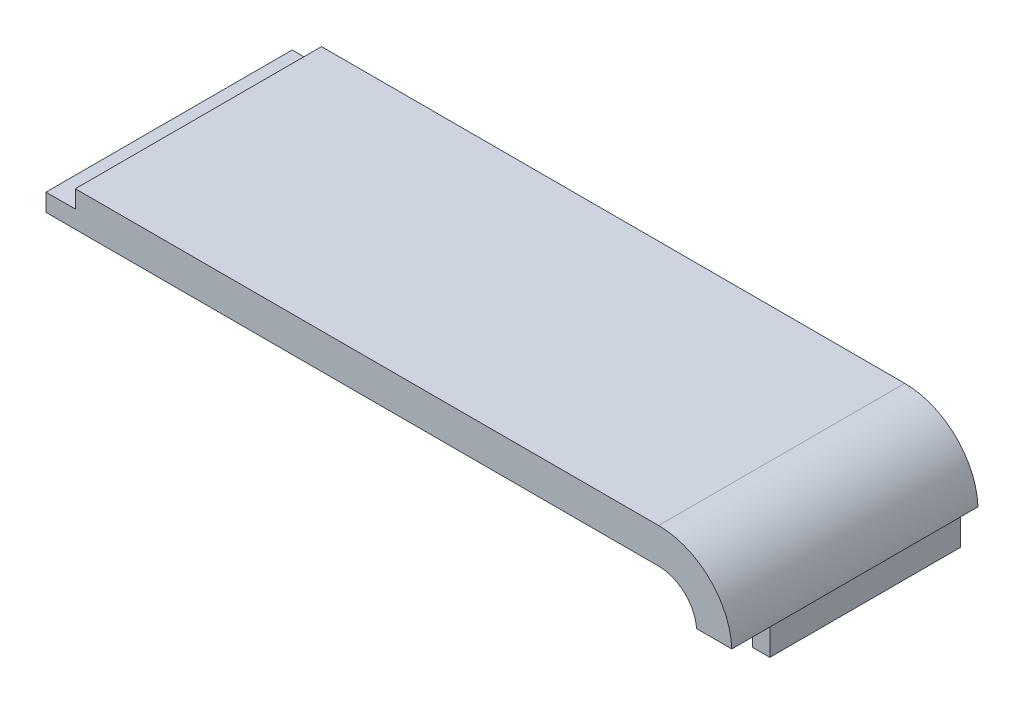
SolidWorks part; units mm, degrees
ref_plane "Front Plane" through (0, 0, 0) normal (0, 0, 1) x (1, 0, 0)
ref_plane "Top Plane" through (0, 0, 0) normal (0, 1, 0) x (1, 0, 0)
ref_plane "Right Plane" through (0, 0, 0) normal (1, 0, 0) x (0, 0, -1)
sketch "Sketch1" plane through (0, 0, 0) normal (0, 0, 1) x (1, 0, 0)
  line L1 (-18.2903, 6.0242) -> (26.5097, 6.0242)
  line L2 (-18.2903, 6.0242) -> (-18.2903, 1.2242)
  line L3 (-18.2903, 1.2242) -> (26.5097, 1.2242)
  line L4 (26.5097, 6.0242) -> (26.5097, 1.2242)
  dimension "D1" = 44.8
  dimension "D2" = 4.8
extrude "Boss-Extrude1" add sketch "Sketch1" along normal blind 16.8
fillet "Fillet1" radius 5 1 edges at (26.5097, 6.0242, 8.4)
sketch "Sketch2" plane through (0, 0, 0) normal (0, 0, -1) x (-1, 0, 0)
  line L1 (-24.106, 1.2242) -> (18.2903, 1.2242)
  line L2 (-21.5137, 3.6242) -> (18.2903, 3.6242)
  line L3 (-21.5137, 3.6242) -> (18.2903, 3.6242)
  line L4 (18.2903, 1.2242) -> (-26.5097, 1.2242) construction
  line L5 (18.2903, 1.2242) -> (18.2903, 3.6242)
  arc A2 (-21.5137, 3.6242) -> (-24.1116, 1.1282) centre (-21.5137, 1.0242) ccw
  arc A3 (-21.5137, 3.6242) -> (-24.106, 1.2242) centre (-21.5137, 1.0242) ccw
  dimension "D1" = 2.4
extrude "Cut-Extrude1" cut sketch "Sketch2" against normal through all
sketch "Sketch3" plane through (0, 1.2242, 0) normal (0, -1, 0) x (1, 0, 0)
  line L0 (24.106, 0) -> (26.5097, 0) construction
  line L2 (24.106, 13) -> (24.106, 0)
  line L3 (24.106, 0) -> (25.306, 0)
  line L4 (25.306, 13) -> (25.306, 0)
  line L5 (24.106, 13) -> (25.306, 13)
  dimension "D1" = 1.2
  dimension "D2" = 13
extrude "Boss-Extrude2" add sketch "Sketch3" along normal blind 3 contours L4 L3 L2 L5
sketch "Sketch4" plane through (-18.2903, 0, 0) normal (-1, 0, 0) x (0, 0, 1)
  line L0 (16.8, 6.0242) -> (16.8, 3.6242) construction
  line L1 (0, 3.6242) -> (16.8, 3.6242)
  line L2 (0, 3.6242) -> (0, 4.8242)
  line L3 (0, 4.8242) -> (16.8, 4.8242)
  line L4 (16.8, 3.6242) -> (16.8, 4.8242)
  dimension "D1" = 1.2
extrude "Boss-Extrude3" add sketch "Sketch4" along normal blind 2
sketch "Sketch5" plane through (0, 0, 0) normal (0, 0, -1) x (-1, 0, 0)
  line L1 (-24.106, -1.7758) -> (-24.106, 1.2242) construction
  line L2 (-18.106, -0.7758) -> (-18.106, 3.6242)
  line L3 (20.2903, 3.6242) -> (-21.5137, 3.6242) construction
  line L4 (-18.106, 3.6242) -> (-21.5137, 3.6242)
  line L5 (-24.106, -0.7758) -> (-24.106, 1.2242)
  line L8 (-24.106, -0.7758) -> (-18.106, -0.7758)
  line L9 (-21.5137, 6.0242) -> (18.2903, 6.0242) construction
  arc A0 (-21.5137, 3.6242) -> (-24.106, 1.2242) centre (-21.5137, 1.0242) ccw
  circle A2 centre (-21.5137, 1.0242) radius 1
  dimension "D3" = 2
  dimension "D1" = 6.8
  dimension "D2" = 6
extrude "Boss-Extrude4" add sketch "Sketch5" against normal blind 2
fillet "Fillet2" radius 2 1 edges at (18.106, -0.7758, 1)
